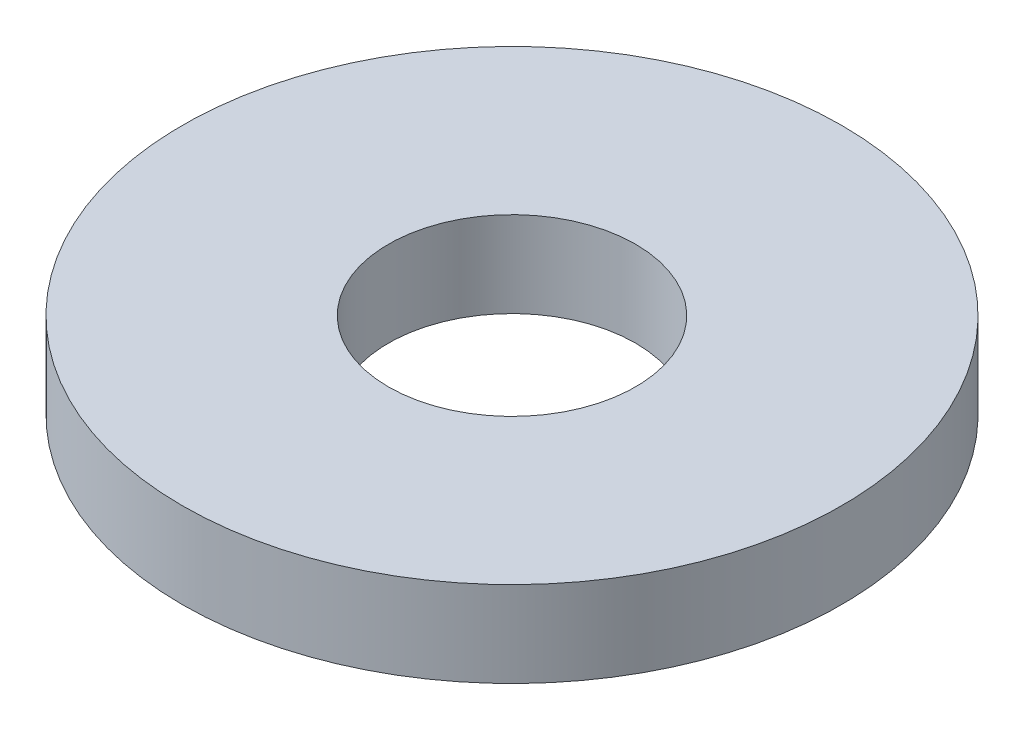
SolidWorks part; units mm, degrees
ref_plane "Front Plane" through (0, 0, 0) normal (0, 0, 1) x (1, 0, 0)
ref_plane "Top Plane" through (0, 0, 0) normal (0, 1, 0) x (1, 0, 0)
ref_plane "Right Plane" through (0, 0, 0) normal (1, 0, 0) x (0, 0, -1)
sketch "Sketch1" plane through (0, 0, 0) normal (0, 1, 0) x (1, 0, 0)
  circle A0 centre (0, 0) radius 100
  dimension "FLANGE_OD" = 200
extrude "Boss-Extrude1" add sketch "Sketch1" along normal blind 26
sketch "Sketch2" plane through (0, 0, 0) normal (0, 1, 0) x (1, 0, 0)
  circle A0 centre (0, 0) radius 37.5
  dimension "BORE_D" = 75
extrude "Cut-Extrude1" cut sketch "Sketch2" along normal through all
sketch "Sketch3" plane through (0, 26, 0) normal (0, 1, 0) x (1, 0, 0)
  circle A0 centre (0, 0) radius 30.1181 construction
  circle A1 centre (-30.1181, 0) radius 7.1641
  dimension "BOLT_D" = 14.3281
  dimension "BOLT_PCD" = 60.2363
extrude "Cut-Extrude2" cut sketch "Sketch3" against normal blind 17.5269 rebuild error yes
pattern_circular "CirPattern1" count 4 over 360 rebuild error yes
